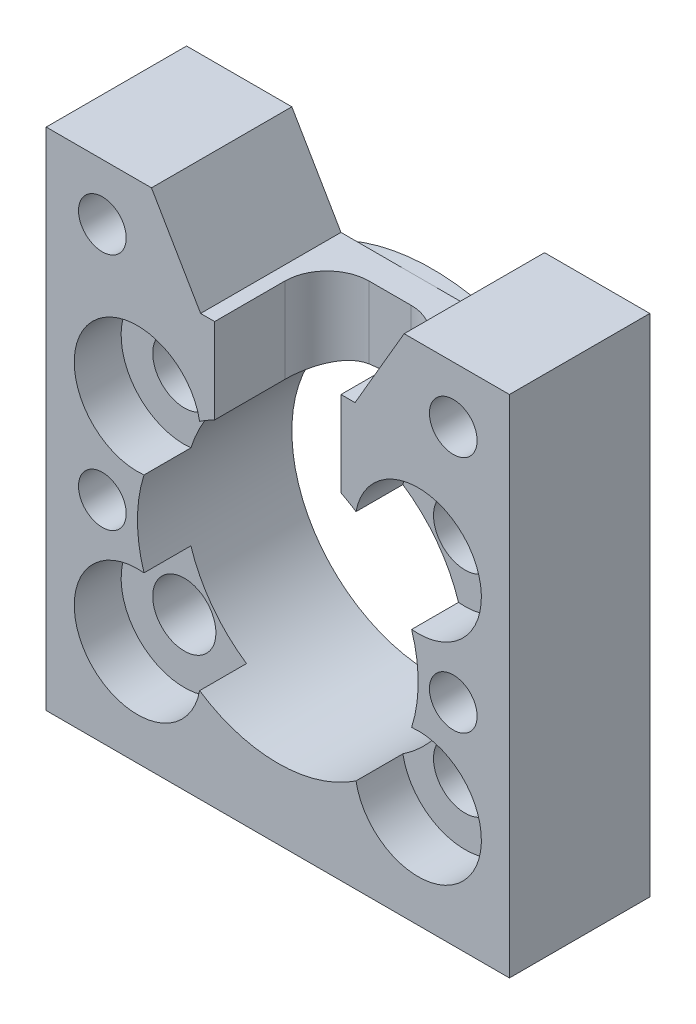
SolidWorks part; units mm, degrees
material "6061 Alloy"
ref_plane "Спереди" through (0, 0, 0) normal (0, 0, 1) x (1, 0, 0)
ref_plane "Сверху" through (0, 0, 0) normal (0, 1, 0) x (1, 0, 0)
ref_plane "Справа" through (0, 0, 0) normal (1, 0, 0) x (0, 0, -1)
other "Configuration Table"
sketch "Sketch1" plane through (0, 0, 0) normal (0, 0, 1) x (1, 0, 0)
  line L0 (-33, 42) -> (-33, -30)
  line L1 (-33, -30) -> (33, -30)
  line L2 (33, -30) -> (33, 42)
  line L3 (33, 42) -> (18, 42)
  line L5 (-18, 42) -> (-33, 42)
  line L6 (0, 48.3077) -> (0, -57.5191) construction
  line L7 (-18, 42) -> (-11, 30)
  line L8 (-25, 34) -> (25, 34) construction
  line L9 (-25, 34) -> (-25, 0) construction
  line L10 (-25, 0) -> (25, 0) construction
  line L11 (25, 34) -> (25, 0) construction
  line L12 (-11, 30) -> (11, 30)
  line L13 (11, 30) -> (18, 42)
  line B0 (-20, -15) -> (20, -15) construction
  line B1 (-20, -15) -> (-20, 15) construction
  line B2 (-20, 15) -> (20, 15) construction
  line B3 (20, -15) -> (20, 15) construction
  line B4 (-20, -15) -> (20, 15) construction
  line B5 (-20, 15) -> (20, -15) construction
  circle B6 centre (0, 0) radius 30
  circle B7 centre (0, 0) radius 20
  dimension "D1" = 66
  dimension "D2" = 8
  dimension "D3" = 34
  dimension "D4" = 15
  dimension "D5" = 22
  dimension "D6" = 8
sketch_block_instance "rsht_mount-1"
sketch_block "rsht_mount" parameters "D1"=60, "D2"=10, "D3"=40, "D4"=30
extrude "Boss-Extrude1" add sketch "Sketch1" along normal blind 20 contours L6 L5 L0 L1 B6 | L6 B6 L1 L2 L3 | B6 L6 B7 | L6 B6 B7 region at (-25.5, 41.208, 0) region at (21.7732, -21.7732, 0) region at (-29.1515, 0, 0)
extrude "Boss-Extrude2" add sketch "Sketch1<3>" against normal blind 2 contours L6 B6 B7 | B6 L6 B7 region at (-29.1515, 0, 0)
sketch "Sketch1<3>" plane through (0, 0, 0) normal (0, 0, 1) x (1, 0, 0) same geometry as "Sketch1"
hole_wizard "CBORE for M8 Hex Head Bolt1" positions "Sketch2" profile "Sketch3" counterbore size "M8" standard "ANSI Metric" end condition through all
sketch "Sketch2" plane through (0, 0, 20) normal (0, 0, 1) x (1, 0, 0)
  point P0 (-20, 15)
  point P3 (20, 15)
  point P6 (-20, -15)
  point P9 (20, -15)
sketch "Sketch3" plane through (-20, 15, 20) normal (1, 0, 0) x (0, -1, 0)
  line L0 (0, 0) -> (0, 22)
  line L1 (0, 22) -> (4.5, 22)
  line L3 (4.5, 22) -> (4.5, 6.68)
  line L4 (4.5, 6.68) -> (9.005, 6.68)
  line L5 (9.005, 6.68) -> (9.005, 0)
  line L7 (9.005, 0) -> (0, 0)
  line L11 (0, -6.35) -> (0, 107.95) construction
  dimension "Thru Hole Dia." = 9
  dimension "Thru Hole Depth" = 22
  dimension "C'Bore Dia." = 18.01
  dimension "C'Bore Depth" = 6.68
hole_wizard "M8x1.25 Tapped Hole1" positions "Sketch4" profile "Sketch5" tap size "M8x1.25" standard "ANSI Metric"
sketch "Sketch4" plane through (0, 0, 20) normal (0, 0, 1) x (1, 0, 0)
  point P0 (-25, 34)
  point P3 (25, 34)
  point P6 (25, 0)
  point P9 (-25, 0)
cosmetic thread "Hole Thread1" parameters "D1"=2.4, "D2"=8
cosmetic thread "Hole Thread2" parameters "D1"=2.4, "D2"=8
cosmetic thread "Hole Thread3" parameters "D1"=2.4, "D2"=8
cosmetic thread "Hole Thread4" parameters "D1"=2.4, "D2"=8
sketch "Sketch5" plane through (-25, 34, 20) normal (1, 0, 0) x (0, -1, 0)
  line L0 (0, 0) -> (0, 22.0429)
  line L1 (0, 22.0429) -> (3.4, 20)
  line L2 (3.4, 20) -> (3.4, 0)
  line L5 (3.4, 0) -> (0, 0)
  line L10 (0, 22.0429) -> (-3.4, 20) construction
  line L11 (0, -6.35) -> (0, 107.95) construction
  dimension "Tap Drill Dia." = 6.8
  dimension "Tap Drill Depth" = 20
  dimension "Drill Angle" = 118
sketch "Sketch7" plane through (0, 0, 0) normal (0, 1, 0) x (1, 0, 0)
  line L0 (-9, -20) -> (9, -20)
  line L1 (-11, -20) -> (11, -20) construction
  line L2 (3, -4) -> (-3, -4)
  line L3 (0, 8.2385) -> (0, -33.5983) construction
  line L4 (9, -10) -> (9, -20)
  line L5 (-9, -10) -> (-9, -20)
  line L6 (0, 0) -> (11, 0) construction
  arc A1 (9, -10) -> (3, -4) centre (3, -10) ccw
  arc A2 (-3, -4) -> (-9, -10) centre (-3, -10) ccw
  dimension "D1" = 6
  dimension "D2" = 6
  dimension "D3" = 4
extrude "Cut-Extrude1" cut sketch "Sketch7" along normal through all
equation "\"D2@Sketch7\"=\"D1@Sketch7\""
